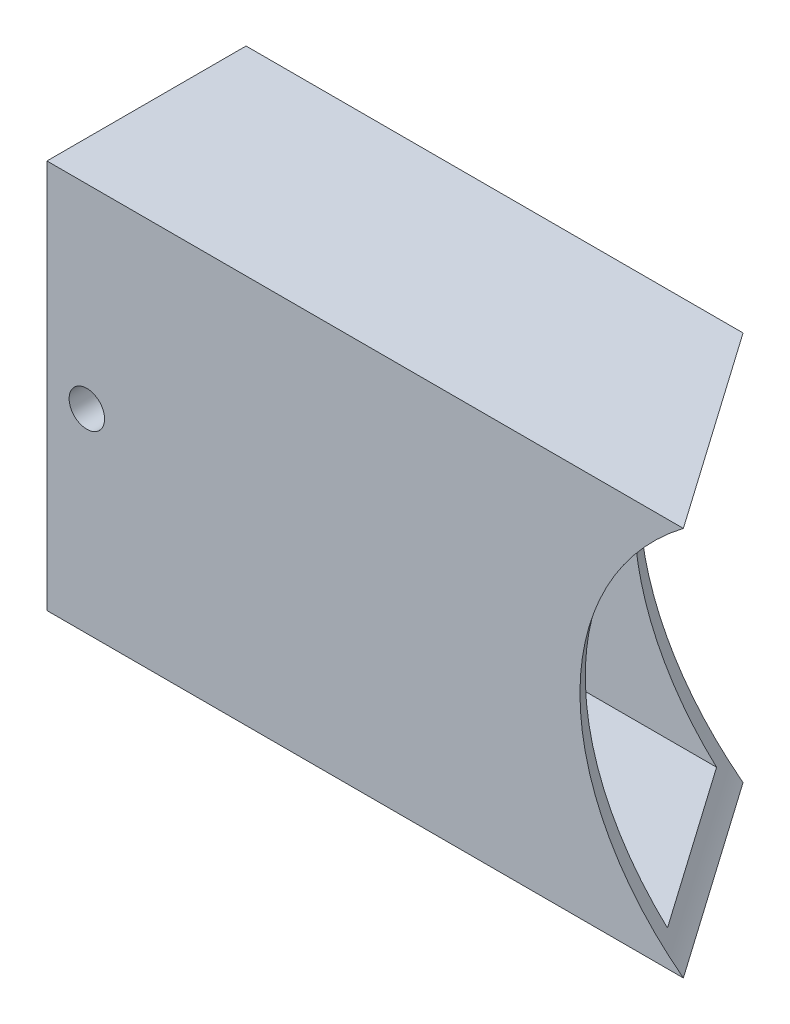
SolidWorks part; units mm, degrees
ref_plane "Płaszczyzna przednia" through (0, 0, 0) normal (0, 0, 1) x (1, 0, 0)
ref_plane "Płaszczyzna górna" through (0, 0, 0) normal (0, 1, 0) x (1, 0, 0)
ref_plane "Płaszczyzna prawa" through (0, 0, 0) normal (1, 0, 0) x (0, 0, -1)
sketch "Sketch1" plane through (0, 0, 0) normal (1, 0, 0) x (0, 0, -1)
  line L0 (-0.6387, 40.2743) -> (-0.6387, -3.6257)
  line L1 (1.3613, 38.2743) -> (19.8113, 38.2743)
  line L2 (1.3613, 38.2743) -> (1.3613, -1.6257)
  line L3 (1.3613, -1.6257) -> (19.8113, -1.6257)
  line L4 (19.8113, 38.2743) -> (19.8113, -1.6257)
  line L5 (-0.6387, -3.6257) -> (21.8113, -3.6257)
  line L6 (21.8113, 40.2743) -> (21.8113, -3.6257)
  line L7 (-0.6387, 40.2743) -> (21.8113, 40.2743)
  dimension "D1" = 2
  dimension "D2" = 39.9
  dimension "D3" = 18.45
extrude "Boss-Extrude1" add sketch "Sketch1" along normal blind 60 and the other way blind 27
ref_plane "Plane1" through (0, 18.3243, 0) normal (0, -1, 0) x (-1, 0, 0)
sketch "Sketch2" plane through (0, 18.3243, 0) normal (0, -1, 0) x (-1, 0, 0)
  line L0 (-79.8539, -15.1106) -> (-55.2794, -32.3179)
  line L1 (-79.8539, -15.1106) -> (-37.7646, 44.9992)
  line L2 (-55.2794, -32.3179) -> (-13.19, 27.7919)
  line L3 (-37.7646, 44.9992) -> (-13.19, 27.7919)
  line L4 (41.6366, 0) -> (-61.7223, 0) construction
  dimension "D1" = 35
  dimension "D2" = 30
revolve "Cut-Revolve1" cut sketch "Sketch2" angle 360 about L1
sketch "Sketch3" plane through (0, 0, 0.6387) normal (0, 0, 1) x (1, 0, 0)
  line L0 (-10.1475, 18.3243) -> (10.1475, 18.3243) construction
  line L1 (-27, 40.2743) -> (-27, -3.6257) construction
  line L2 (-53.7248, 18.3243) -> (-31.375, 18.3243) construction
  line L3 (-27, 22.8533) -> (-17.3022, 22.8533)
  line L4 (-27, 22.8533) -> (-27, 13.7954)
  line L5 (-27, 13.7954) -> (-17.3022, 13.7954)
  line L6 (-17.3022, 22.8533) -> (-17.3022, 13.7954)
  circle A0 centre (-22.5, 18.3243) radius 2
  dimension "D1" = 4
  dimension "D2" = 4.5
extrude "Boss-Extrude2" add sketch "Sketch3" against normal blind 6
extrude "Cut-Extrude1" cut sketch "Sketch3<3>" against normal up to next contours A0
sketch "Sketch3<3>" plane through (0, 0, 0.6387) normal (0, 0, 1) x (1, 0, 0) same geometry as "Sketch3"
equation "\"exitheight\"= 18.45"
equation "\"exitwidth\"= 40"
equation "\"outerdiameter\"= 30"
equation "\"wallthick\"= 2"
equation "\"D2@Sketch2\"=\"outerdiameter\""
